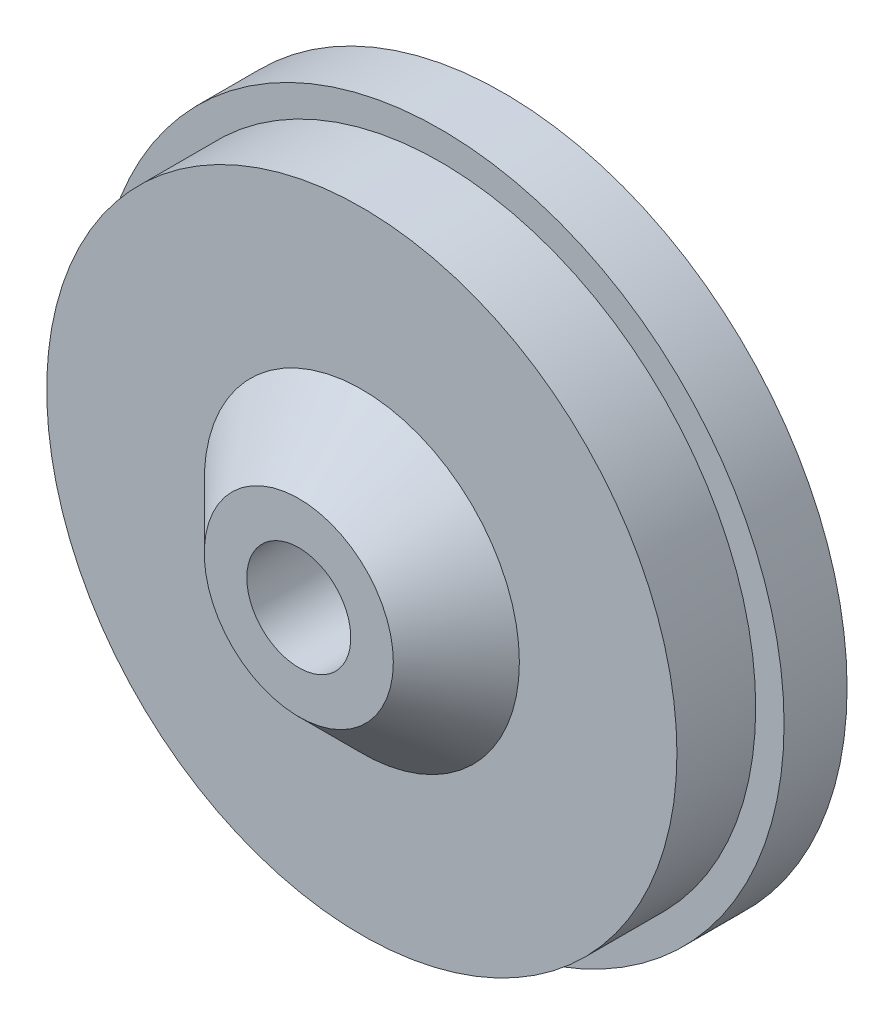
SolidWorks part; units mm, degrees
ref_plane "Front Plane" through (0, 0, 0) normal (0, 0, 1) x (1, 0, 0)
ref_plane "Top Plane" through (0, 0, 0) normal (0, 1, 0) x (1, 0, 0)
ref_plane "Right Plane" through (0, 0, 0) normal (1, 0, 0) x (0, 0, -1)
sketch "Sketch1" plane through (0, 0, 0) normal (0, 0, 1) x (1, 0, 0)
  circle A0 centre (0, 0) radius 10.9
  dimension "D1" = 21.8
extrude "Boss-Extrude1" add sketch "Sketch1" along normal blind 2
sketch "Sketch2" plane through (0, 0, 2) normal (0, 0, 1) x (1, 0, 0)
  circle A0 centre (0, 0) radius 10
  dimension "D1" = 20
extrude "Boss-Extrude2" add sketch "Sketch2" along normal blind 2.5
sketch "Sketch4" plane through (0, 0, 4.5) normal (0, 0, 1) x (1, 0, 0)
  circle A0 centre (0, 0) radius 3
  dimension "D1" = 6
extrude "Boss-Extrude3" add sketch "Sketch4" along normal blind 2
sketch "Sketch3" plane through (0, 0, 0) normal (0, 0, -1) x (-1, 0, 0)
  circle A0 centre (0, 0) radius 1.65
  dimension "D1" = 3.3
extrude "Cut-Extrude1" cut sketch "Sketch3" against normal through all
chamfer "Chamfer1" distance 2 angle 45 1 edges at (3, 0, 4.5)
